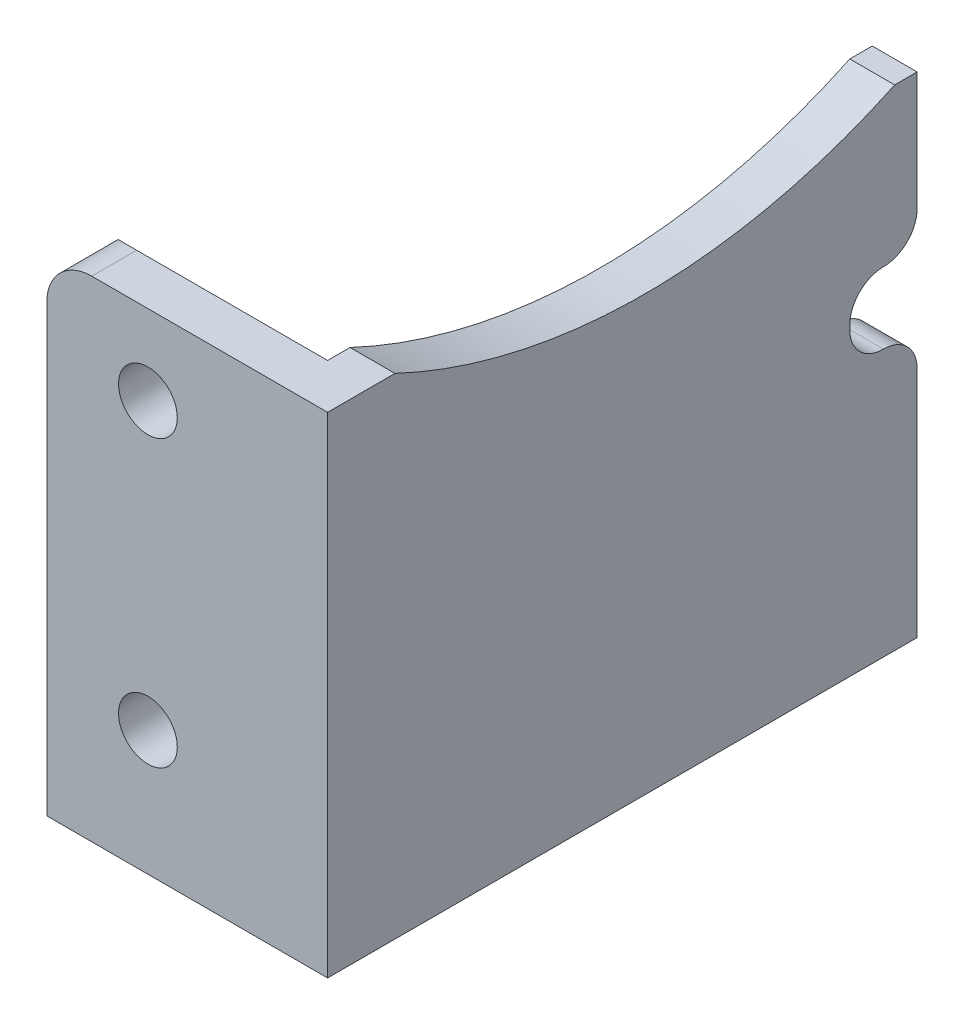
SolidWorks part; units mm, degrees
ref_plane "Front Plane" through (0, 0, 0) normal (0, 0, 1) x (1, 0, 0)
ref_plane "Top Plane" through (0, 0, 0) normal (0, 1, 0) x (1, 0, 0)
ref_plane "Right Plane" through (0, 0, 0) normal (1, 0, 0) x (0, 0, -1)
sketch "Sketch1" plane through (0, 0, 0) normal (0, 0, 1) x (1, 0, 0)
  line L0 (-4, 0) -> (-4, -47.625) construction
  line L1 (0, 0) -> (-25, 0)
  line L2 (0, 0) -> (0, -47.625)
  line L3 (0, -47.625) -> (-25, -47.625)
  line L4 (-25, 0) -> (-25, -47.625)
  line L5 (-16, -11.1125) -> (-16, -36.5125) construction
  line L6 (0, -23.8125) -> (-25, -23.8125) construction
  circle A0 centre (-16, -11.1125) radius 2.6162
  circle A1 centre (-16, -36.5125) radius 2.6162
  point P11 (-16, -23.8125)
  point P14 (0, 0)
  dimension "D3" = 5.2324
  dimension "D1" = 47.625
  dimension "D2" = 25
  dimension "D4" = 12
  dimension "D5" = 4
  dimension "D6" = 25.4
extrude "Boss-Extrude1" add sketch "Sketch1" against normal blind 6
sketch "Sketch3" plane through (0, 0, 0) normal (1, 0, 0) x (0, 0, -1)
  line L0 (6, -47.625) -> (0, -47.625) construction
  line L1 (0, 0) -> (52.5, 0)
  line L2 (0, 0) -> (0, -47.625)
  line L3 (0, -47.625) -> (52.5, -47.625)
  line L4 (52.5, 0) -> (52.5, -47.625)
  point P4 (0, -47.625)
  dimension "D1" = 52.5
extrude "Boss-Extrude2" add sketch "Sketch3" against normal up to vertex (4 mm away) up to point (-4, -47.625, 0)
sketch "Sketch4" plane through (0, -47.625, 0) normal (0, -1, 0) x (1, 0, 0)
  line L0 (-25, -6) -> (-4, -52.5)
  line L1 (-4, -52.5) -> (-4, -6)
  line L2 (-4, -6) -> (-25, -6)
extrude "Boss-Extrude3" add sketch "Sketch4" against normal blind 3
sketch "Sketch5" plane through (0, 0, -6) normal (0, 0, -1) x (-1, 0, 0)
  line L1 (25, 0) -> (0, 0)
  line L2 (25, 0) -> (25, -4)
  line L3 (25, -4) -> (0, -4)
  line L4 (0, 0) -> (0, -4)
  line L5 (0, 0) -> (0, -47.625) construction
  point P4 (0, -4)
  dimension "D1" = 4
extrude "Cut-Extrude1" cut sketch "Sketch5" against normal through all and the other way through all
chamfer "Chamfer1" distance 2 angle 45 1 edges at (-14.5, -4, -6)
sketch "Sketch6" plane through (-4, 0, 0) normal (-1, 0, 0) x (0, 0, 1)
  line L0 (-52.5, -44.625) -> (-52.5, -4) construction
  line L1 (-52.5, -17.526) -> (-46.5, -17.526)
  line L2 (-52.5, -17.526) -> (-52.5, -23.876)
  line L3 (-52.5, -23.876) -> (-46.5, -23.876)
  line L4 (-46.5, -17.526) -> (-46.5, -23.876)
  line L5 (-52.5, -20.701) -> (-46.5, -20.701) construction
  line L6 (-6, -47.625) -> (-52.5, -47.625) construction
  dimension "D1" = 26.924
  dimension "D2" = 6.35
  dimension "D3" = 6
extrude "Cut-Extrude2" cut sketch "Sketch6" against normal through all
sketch "Sketch7" plane through (-4, 0, 0) normal (-1, 0, 0) x (0, 0, 1)
  line L0 (-4, -4) -> (-52.5, -4) construction
  line L1 (-52.5, -17.526) -> (-52.5, -4) construction
  line L2 (-50.5, -4) -> (-6, -4)
  arc A0 (-50.5, -4) -> (-6, -4) centre (-28.25, 43.0062) ccw
  point P8 (-28.25, -9)
  dimension "D1" = 2
  dimension "D2" = 2
  dimension "D3" = 5
extrude "Cut-Extrude3" cut sketch "Sketch7" against normal through all
fillet "Fillet2" radius 3 4 edges at (-2, -17.526, -52.5) (-2, -17.526, -46.5) (-2, -23.876, -52.5) (-2, -23.876, -46.5)
fillet "Fillet1" radius 3 1 edges at (-4, -25.3125, -6)
fillet "Fillet3" radius 4 1 edges at (-25, -4, -2)
